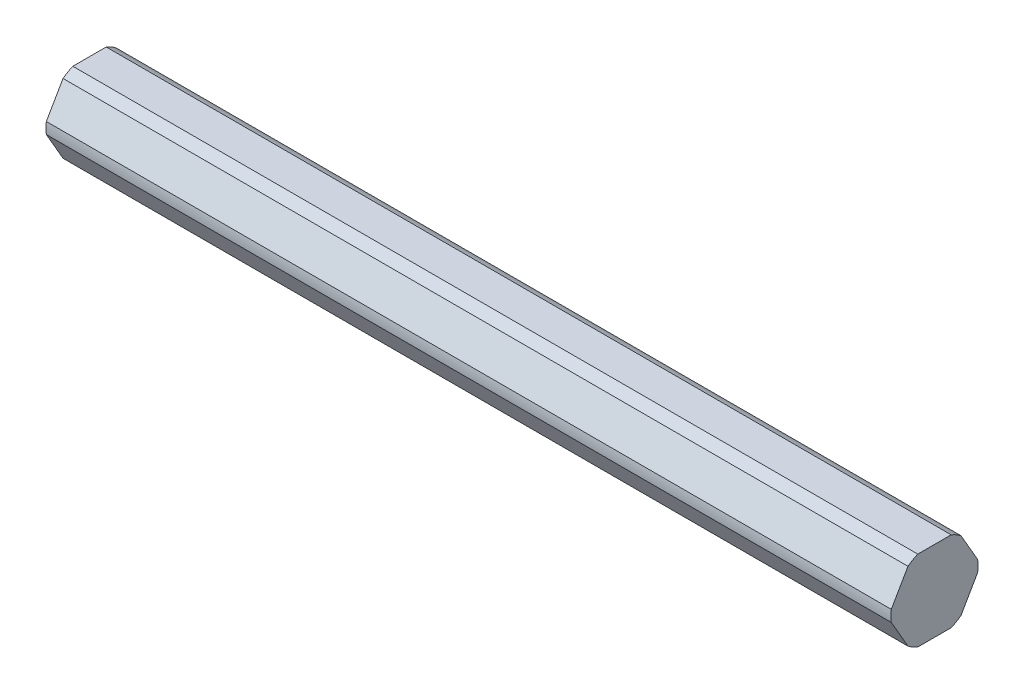
SolidWorks part; units mm, degrees
ref_plane "Front Plane" through (0, 0, 0) normal (0, 0, 1) x (1, 0, 0)
ref_plane "Top Plane" through (0, 0, 0) normal (0, 1, 0) x (1, 0, 0)
ref_plane "Right Plane" through (0, 0, 0) normal (1, 0, 0) x (0, 0, -1)
sketch "Sketch1" plane through (0, 0, 0) normal (1, 0, 0) x (0, 0, -1)
  line L1 (2.635, 6.35) -> (-2.635, 6.35)
  line L2 (-4.1818, 5.457) -> (-6.8168, 0.893)
  line L3 (-6.8168, -0.893) -> (-4.1818, -5.457)
  line L4 (-2.635, -6.35) -> (2.635, -6.35)
  line L5 (4.1818, -5.457) -> (6.8168, -0.893)
  line L6 (6.8168, 0.893) -> (4.1818, 5.457)
  circle A0 centre (0, 0) radius 6.35 construction
  arc A1 (-2.635, 6.35) -> (-4.1818, 5.457) centre (0, 0) ccw
  arc A2 (4.1818, 5.457) -> (2.635, 6.35) centre (0, 0) ccw
  arc A3 (6.8168, -0.893) -> (6.8168, 0.893) centre (0, 0) ccw
  arc A4 (2.635, -6.35) -> (4.1818, -5.457) centre (0, 0) ccw
  arc A5 (-4.1818, -5.457) -> (-2.635, -6.35) centre (0, 0) ccw
  arc A6 (-6.8168, 0.893) -> (-6.8168, -0.893) centre (0, 0) ccw
  dimension "D2" = 13.75
  dimension "D1" = 12.7
extrude "Boss-Extrude1" add sketch "Sketch1" along normal mid plane 133.35
